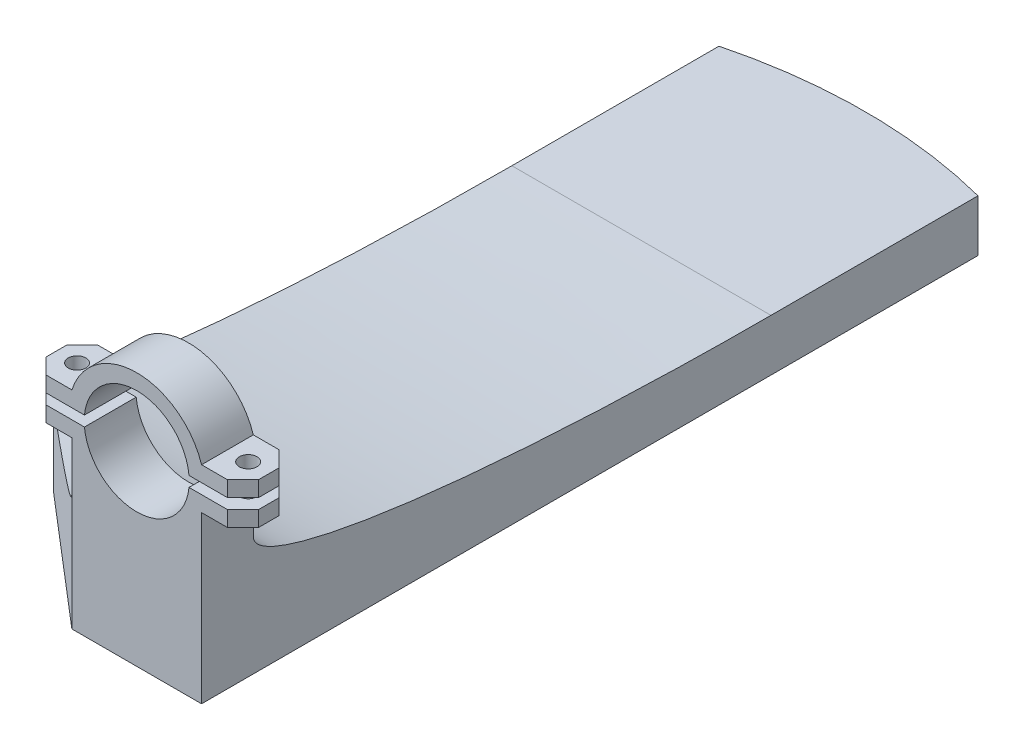
SolidWorks part; units mm, degrees
material "PET"
ref_plane "Front Plane" through (0, 0, 0) normal (0, 0, 1) x (1, 0, 0)
ref_plane "Top Plane" through (0, 0, 0) normal (0, 1, 0) x (1, 0, 0)
ref_plane "Right Plane" through (0, 0, 0) normal (1, 0, 0) x (0, 0, -1)
sketch "Sketch1" plane through (0, 0, 0) normal (0, 0, 1) x (1, 0, 0)
  line L0 (55, 0) -> (-55, 0) construction
  line L1 (-20.5269, -1) -> (-10.1006, -1)
  line L3 (-20.5269, 1) -> (-10.1006, 1)
  line L5 (-27.2535, 0) -> (26.6027, 0) construction
  line L6 (10.1006, 1) -> (20.5269, 1)
  line L7 (-12.5269, 4) -> (-20.5269, 4)
  line L9 (-10.1006, 1) -> (-20.5269, 1)
  line L10 (-20.5269, 4) -> (-20.5269, 1)
  line L11 (-10.1006, -1) -> (-20.5269, -1)
  line L12 (-20.5269, -4) -> (-20.5269, -1)
  line L13 (-12.5269, -4) -> (-20.5269, -4)
  line L15 (0, -55) -> (0, 55) construction
  line L17 (12.5269, -4) -> (20.5269, -4)
  line L18 (20.5269, -4) -> (20.5269, -1)
  line L19 (10.1006, -1) -> (20.5269, -1)
  line L20 (10.1006, 1) -> (20.5269, 1)
  line L21 (20.5269, 4) -> (20.5269, 1)
  line L22 (12.5269, 4) -> (20.5269, 4)
  line L24 (10.1006, 1) -> (20.5269, 1)
  line L25 (20.5269, -1) -> (10.1006, -1)
  line L26 (-20.5269, 1) -> (-10.1006, 1)
  line L27 (-10.1006, -1) -> (-20.5269, -1)
  line L28 (10.1006, -1) -> (20.5269, -1)
  line L31 (-12.5269, -4) -> (-12.5269, -36)
  line L32 (-12.5269, -36) -> (12.5269, -36)
  line L33 (12.5269, -4) -> (12.5269, -36)
  arc A0 (-10.1006, -1) -> (10.1006, -1) centre (0, 0) ccw
  arc A3 (10.1006, 1) -> (-10.1006, 1) centre (0, 0) ccw
  arc A4 (12.5269, 4) -> (-12.5269, 4) centre (0, 0) ccw
  dimension "D1" = 2
  dimension "D2" = 20.3
  dimension "D3" = 3
  dimension "D4" = 8
  dimension "D5" = 3
  dimension "D6" = 32
extrude "Boss-Extrude1" add sketch "Sketch1" along normal mid plane 10 contours L22 A4 L7 L10 L3 A3 L6 L21 | L13 L17 L18 L19 A0 L1 L12 region at (0, -19.9858, 0) region at (-20.0987, 2.5, 0)
sketch "Sketch2" plane through (0, 4, 0) normal (0, 1, 0) x (1, 0, 0)
  line L0 (-20.5269, 5) -> (-12.5269, -5) construction
  line L1 (-20.5269, -5) -> (-12.5269, 5) construction
  line L2 (20.5269, 5) -> (12.5269, -5) construction
  line L3 (20.5269, -5) -> (12.5269, 5) construction
  point P8 (-16.5269, 0)
  point P17 (16.5269, 0)
hole_wizard "M3 Clearance Hole1" positions "Sketch3" profile "Sketch4" hole size "M3" standard "ANSI Metric" end condition through all
sketch "Sketch3" plane through (0, 4, 0) normal (0, 1, 0) x (1, 0, 0)
  point P0 (-16.5269, 0)
  point P3 (16.5269, 0)
sketch "Sketch4" plane through (-16.5269, 4, 0) normal (1, 0, 0) x (0, 0, 1)
  line L0 (0, 0) -> (0, 40)
  line L1 (0, 40) -> (1.7, 40)
  line L2 (1.7, 40) -> (1.7, 0)
  line L5 (1.7, 0) -> (0, 0)
  line L11 (0, -6.35) -> (0, 107.95) construction
  dimension "Thru Hole Dia." = 3.4
  dimension "Thru Hole Depth" = 40
sketch "Sketch5" plane through (0, 0, -5) normal (0, 0, -1) x (-1, 0, 0)
  line L0 (12.5269, -4) -> (12.5269, -36) construction
  line L1 (-12.5269, -36) -> (12.5269, -36)
  line L2 (-12.5269, -36) -> (-12.5269, -26)
  line L3 (-12.5269, -26) -> (12.5269, -26)
  line L4 (12.5269, -36) -> (12.5269, -26)
  dimension "D1" = 10
extrude "Boss-Extrude2" add sketch "Sketch5" along normal blind 140
chamfer "Chamfer2" distance 3 angle 45 4 edges at (-20.5269, 2.5, 5) (-20.5269, 2.5, -5) (20.5269, 2.5, -5) (20.5269, 2.5, 5)
chamfer "Chamfer3" distance 3 angle 45 4 edges at (-20.5269, -2.5, 5) (-20.5269, -2.5, -5) (20.5269, -2.5, 5) (20.5269, -2.5, -5)
sketch "Sketch6" plane through (0, -26, 0) normal (0, 1, 0) x (1, 0, 0)
  line L0 (-12.5269, 145) -> (-12.5269, 5) construction
  line L1 (-37.5269, 145.0139) -> (-37.5269, 16.4107)
  line L2 (-37.5269, 16.4107) -> (-12.5269, -5)
  line L3 (-12.5269, -5) -> (12.5269, 145)
  arc A0 (12.5269, 145) -> (-37.5269, 145.0139) centre (-12.5269, 48.1893) ccw
  point P6 (-6.5235, 46.8313)
  point P9 (-12.5269, 48.3361)
  dimension "D2" = 100
  dimension "D1" = 25
extrude "Boss-Extrude3" add sketch "Sketch6" against normal up to surface (10 mm away) up to face at (0, -36, -70)
fillet "Fillet1" radius 13 2 edges at (-12.5269, -26, 0) (0, -26, -5) second distance 100 first distance on face at (-12.5269, -15, 0) first distance on face at (0, -8.115, -5)
